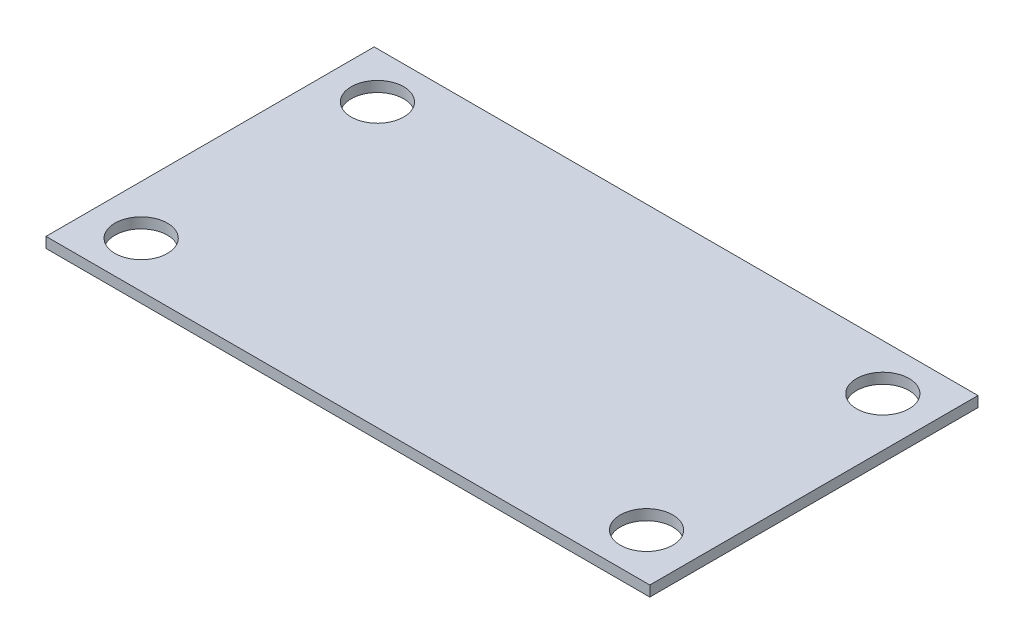
SolidWorks part; units mm, degrees
ref_plane "前视基准面" through (0, 0, 0) normal (0, 0, 1) x (1, 0, 0)
ref_plane "上视基准面" through (0, 0, 0) normal (0, 1, 0) x (1, 0, 0)
ref_plane "右视基准面" through (0, 0, 0) normal (1, 0, 0) x (0, 0, -1)
other "Configuration Table"
sketch "草图1" plane through (0, 0, 0) normal (0, 1, 0) x (1, 0, 0)
  line L0 (-46, 0) -> (46.2143, 0) construction
  line L1 (-46, 25) -> (46, 25)
  line L2 (-46, 25) -> (-46, -25)
  line L3 (-46, -25) -> (46, -25)
  line L4 (46, 25) -> (46, -25)
  line L7 (0, 25) -> (0, -30.3232) construction
  circle A2 centre (-38.5, -18) radius 4
  circle A3 centre (38.5, -18) radius 4
  circle A4 centre (38.5, 18) radius 4
  circle A5 centre (-38.5, 18) radius 4
  dimension "D3" = 7.5
  dimension "D4" = 8
  dimension "D1" = 50
  dimension "D2" = 92
  dimension "D5" = 7
extrude "凸台-拉伸1" add sketch "草图1" along normal blind 1.6
